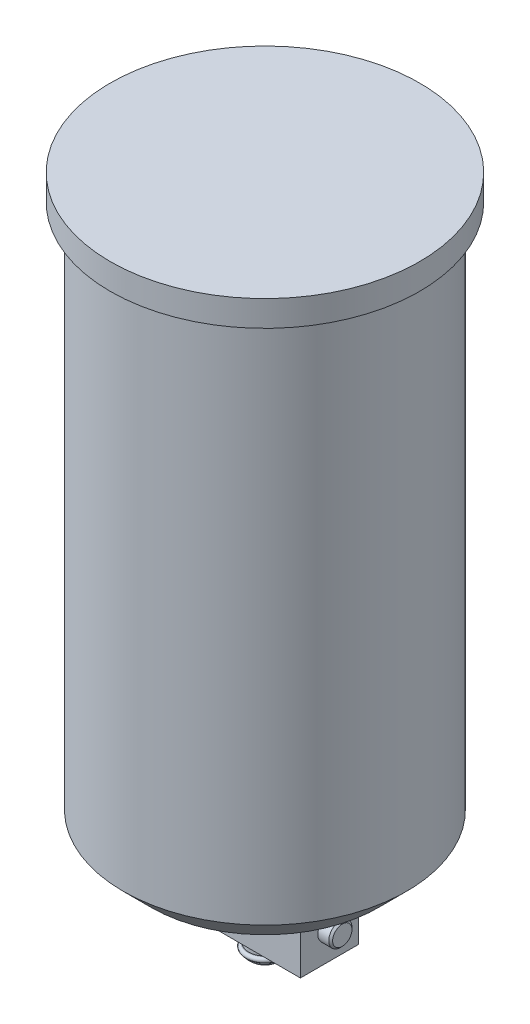
SolidWorks part; units mm, degrees
ref_plane "前视基准面" through (0, 0, 0) normal (0, 0, 1) x (1, 0, 0)
ref_plane "上视基准面" through (0, 0, 0) normal (0, 1, 0) x (1, 0, 0)
ref_plane "右视基准面" through (0, 0, 0) normal (1, 0, 0) x (0, 0, -1)
sketch "草图1" plane through (0, 0, 0) normal (0, 0, 1) x (1, 0, 0)
  line L0 (0, 90) -> (24, 90)
  line L1 (24, 90) -> (24, 86)
  line L2 (24, 86) -> (22, 86)
  line L3 (22, 86) -> (22, 4.4)
  line L4 (22, 4.4) -> (17.6, 0)
  line L5 (17.6, 0) -> (0, 0)
  line L6 (0, 0) -> (0, 90)
  line L7 (0, 0) -> (0, 90) construction
revolve "旋转1" add sketch "草图1" angle 360 about L7 reverse direction yes
sketch "草图2" plane through (0, 0, 0) normal (0, 1, 0) x (1, 0, 0)
  line L0 (-10, -4.5) -> (10, -4.5)
  line L1 (10, -4.5) -> (10, 4.5)
  line L2 (10, 4.5) -> (-10, 4.5)
  line L3 (-10, 4.5) -> (-10, -4.5)
extrude "凸台-拉伸1" add sketch "草图2" against normal blind 11
sketch "草图3" plane through (0, 0, 0) normal (0, 1, 0) x (1, 0, 0)
  line L0 (-10, -5.5) -> (10, -5.5)
  line L1 (10, -5.5) -> (10, 5.5)
  line L2 (10, 5.5) -> (-10, 5.5)
  line L3 (-10, 5.5) -> (-10, -5.5)
extrude "凸台-拉伸2" add sketch "草图3" against normal blind 2
sketch "草图4" plane through (0, 0, 0) normal (0, 0, 1) x (1, 0, 0)
  line L0 (0, -11) -> (2.5, -11)
  line L1 (2.5, -11) -> (2.5, -13.5333)
  line L2 (2.5, -13.5333) -> (2.6, -13.5333)
  line L3 (2.6, -14.3333) -> (2.5, -14.3333)
  line L4 (2.5, -14.3333) -> (2.5, -14.6667)
  line L5 (2.5, -14.6667) -> (2.1429, -14.6667)
  line L6 (2.1429, -14.6667) -> (2.1429, -15)
  line L7 (2.1429, -15) -> (0, -15)
  line L8 (0, -15) -> (0, -11)
  line L9 (0, -15) -> (0, -11) construction
  arc A0 (2.6, -13.5333) -> (3, -13.9333) centre (2.6, -13.9333) cw
  arc A1 (3, -13.9333) -> (2.6, -14.3333) centre (2.6, -13.9333) cw
revolve "旋转2" add sketch "草图4" angle 360 about L9 reverse direction yes
sketch "草图5" plane through (0, 0, 0) normal (0, 0, 1) x (1, 0, 0)
  line L0 (-11, -6.5) -> (-11, -5.825)
  line L1 (-11, -5.825) -> (-10.775, -5.6)
  line L2 (-10.775, -5.6) -> (9.5, -5.6)
  line L3 (9.5, -5.6) -> (9.5, -4.7)
  line L4 (9.5, -4.7) -> (11.7, -4.7)
  line L5 (11.7, -4.7) -> (12, -5)
  line L6 (12, -5) -> (12, -6.5)
  line L7 (12, -6.5) -> (-11, -6.5)
  line L8 (12, -6.5) -> (-11, -6.5) construction
revolve "旋转3" add sketch "草图5" angle 360 about L8 reverse direction yes
ref_plane "基准面4" through (0, 90, 0) normal (0, 1, 0) x (1, 0, 0)
ref_plane "case XY" through (0, 90, 0) normal (0, 1, 0) x (1, 0, 0)
ref_plane "case XZ" through (0, 0, 0) normal (0, 0, 1) x (1, 0, 0)
ref_plane "case YZ" through (0, 0, 0) normal (1, 0, 0) x (0, 0, -1)
ref_axis "case X" through (-80.9, 90, 0) along (1, 0, 0)
ref_axis "case Y" through (0, 90, 50) along (0, 0, -1)
ref_axis "case Z" through (0, 50, 0) along (0, -1, 0)
sketch3d "case"
  point P0 (0, 90, 0)
